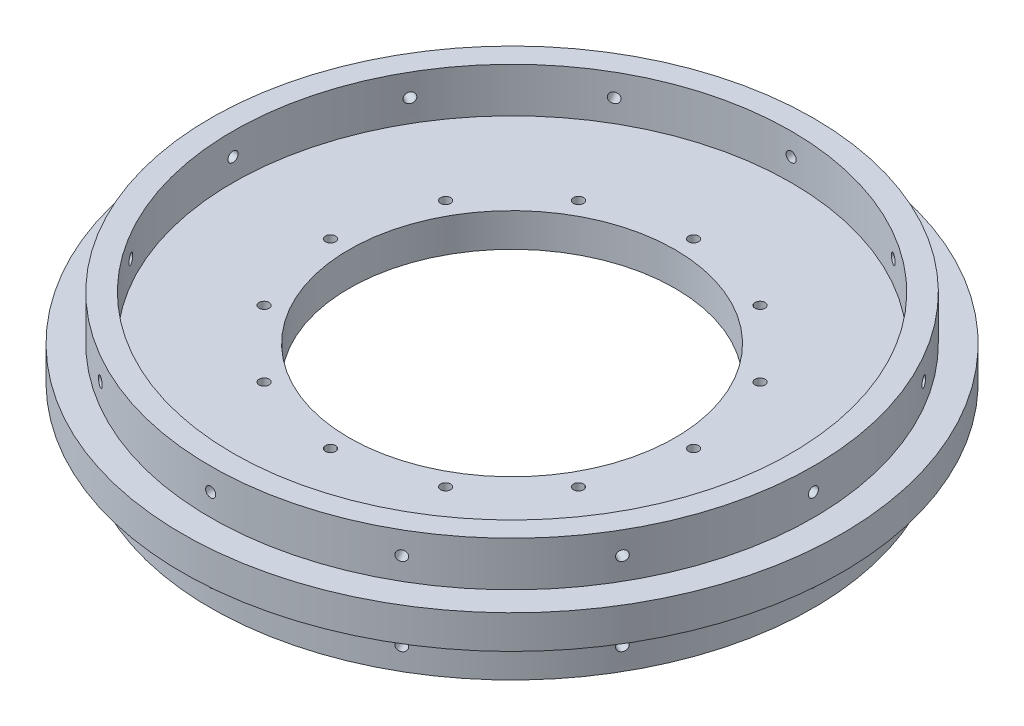
SolidWorks part; units mm, degrees
material "6061-T6 (SS)"
ref_plane "Front Plane" through (0, 0, 0) normal (0, 0, 1) x (1, 0, 0)
ref_plane "Top Plane" through (0, 0, 0) normal (0, 1, 0) x (1, 0, 0)
ref_plane "Right Plane" through (0, 0, 0) normal (1, 0, 0) x (0, 0, -1)
sketch "Sketch1" plane through (0, 0, 0) normal (0, 1, 0) x (1, 0, 0)
  line L5 (0, 0) -> (127.635, 0)
  line L6 (0, 0) -> (0, 127.635)
  line L7 (0, 127.635) -> (127.635, 127.635)
  line L8 (127.635, 0) -> (127.635, 127.635)
  dimension "D1" = 127.635
  dimension "D2" = 127.635
extrude "Boss-Extrude1" add sketch "Sketch1" along normal blind 9.525 contours L5 L8 L7 L6
sketch "Sketch12" plane through (0, 0, 0) normal (0, -1, 0) x (1, 0, 0)
  line L0 (63.8175, 0) -> (63.8175, -127.635) construction
  line L1 (0, 0) -> (127.635, 0) construction
  line L2 (0, -127.635) -> (127.635, -127.635) construction
  line L3 (0, -63.8175) -> (127.635, -63.8175) construction
  line L4 (0, 0) -> (0, -127.635) construction
  line L5 (127.635, 0) -> (127.635, -127.635) construction
  circle A0 centre (63.8175, -63.8175) radius 93.726
  dimension "D1" = 187.452
extrude "Boss-Extrude2" add sketch "Sketch12" against normal up to surface (9.525 mm away) contours A0 up to face at (63.8175, 9.525, -63.8175)
sketch "Sketch5" plane through (0, 9.525, 0) normal (0, 1, 0) x (1, 0, 0)
  circle A0 centre (63.8175, 63.8175) radius 46.355
  circle A3 centre (63.8175, 63.8175) radius 93.726 construction
  dimension "D1" = 92.71
extrude "Cut-Extrude1" cut sketch "Sketch5" against normal blind 9.525
sketch "Sketch11" plane through (0, 9.525, 0) normal (0, 1, 0) x (1, 0, 0)
  line L0 (63.8175, 63.8175) -> (63.8175, 115.443) construction
  circle A0 centre (63.8175, 115.443) radius 1.4351
  dimension "D2" = 2.8702
  dimension "D1" = 51.6255
extrude "Cut-Extrude3" cut sketch "Sketch11" against normal through all contours A0
pattern_circular "CirPattern1" count 12 over 360 about axis through (63.8175, 9.525, -63.8175) along (0, 1, 0) of "Cut-Extrude3"
sketch "Sketch14" plane through (0, 9.525, 0) normal (0, -1, 0) x (1, 0, 0)
  line L0 (63.8175, -63.8175) -> (147.6375, -63.8175) construction
  line L1 (0, -19.2087) -> (0, 19.2087) construction
  line L2 (147.6375, -63.8175) -> (152.7175, -63.8175)
  line L3 (136.3808, -105.7742) -> (140.8401, -108.2104)
  circle A0 centre (63.8175, -63.8175) radius 46.355 construction
  arc A2 (147.6375, -63.8175) -> (136.3808, -105.7742) centre (63.8175, -63.8175) cw
  arc A3 (152.7175, -63.8175) -> (140.8401, -108.2104) centre (63.8175, -63.8175) cw
  point P0 (63.8175, -63.8175)
  dimension "D1" = 83.82
  dimension "D2" = 88.9
  dimension "D3" = 46.482
  dimension "D4" = 43.942
ref_plane "Support mirror reference plane" through (0, 4.7625, 0) normal (0, 1, 0) x (1, 0, 0)
sketch "Sketch25" plane through (0, 9.525, 0) normal (0, -1, 0) x (1, 0, 0)
  line L0 (63.8175, -63.8175) -> (123.0872, -4.5478) construction
  line L2 (123.0872, -4.5478) -> (126.6793, -0.9557)
  line L3 (144.7953, -42.1754) -> (149.6712, -40.7448)
  line L5 (63.8175, -63.8175) -> (147.6375, -63.8175) construction
  arc A2 (123.0872, -4.5478) -> (144.7953, -42.1754) centre (63.8175, -63.8175) cw
  arc A3 (126.6793, -0.9557) -> (149.6712, -40.7448) centre (63.8175, -63.8175) cw
  point P0 (63.8175, -63.8175)
  dimension "D1" = 83.82
  dimension "D2" = 88.9
  dimension "D3" = 46.482
  dimension "D4" = 43.942
  dimension "D5" = 45
sketch "Sketch30" plane through (0, 0, 0) normal (0, -1, 0) x (1, 0, 0)
  circle A0 centre (63.8175, -63.8175) radius 85.725
  circle A1 centre (63.8175, -63.8175) radius 79.375
  dimension "D1" = 171.45
  dimension "D2" = 158.75
extrude "Boss-Extrude3" add sketch "Sketch30" along normal blind 12.7
mirror "Mirror1" about plane through (0, 4.7625, 0) normal (0, 1, 0) of "Boss-Extrude3"
sketch "Sketch31" plane through (0, 0, 0) normal (0, -1, 0) x (-1, 0, 0)
  line L0 (-63.8175, -52.481) -> (-63.8175, 177.7216) construction
ref_plane "Plane1" through (0, 0, -149.5425) normal (0, 0, -1) x (-1, 0, 0)
ref_plane "Plane2" through (63.8175, 0, 0) normal (-1, 0, 0) x (0, 0, -1)
sketch "Sketch32" plane through (0, 0, -149.5425) normal (0, 0, -1) x (-1, 0, 0)
  line L4 (-63.8175, -87.3125) -> (-63.8175, 87.3125) construction
  line L5 (-149.5425, 0) -> (21.9075, 0) construction
  line L6 (21.9075, 9.525) -> (-149.5425, 9.525) construction
  circle A0 centre (-63.8175, -6.35) radius 1.4351
  circle A1 centre (-63.8175, 15.875) radius 1.4351
  dimension "D1" = 2.8702
  dimension "D2" = 2.8702
  dimension "D3" = 6.35
  dimension "D4" = 6.35
extrude "Cut-Extrude4" cut sketch "Sketch32" against normal blind 15.24
pattern_circular "CirPattern2" count 12 over 360 about axis through (63.8175, -12.7, -63.8175) along (0, 1, 0) of "Cut-Extrude4"
